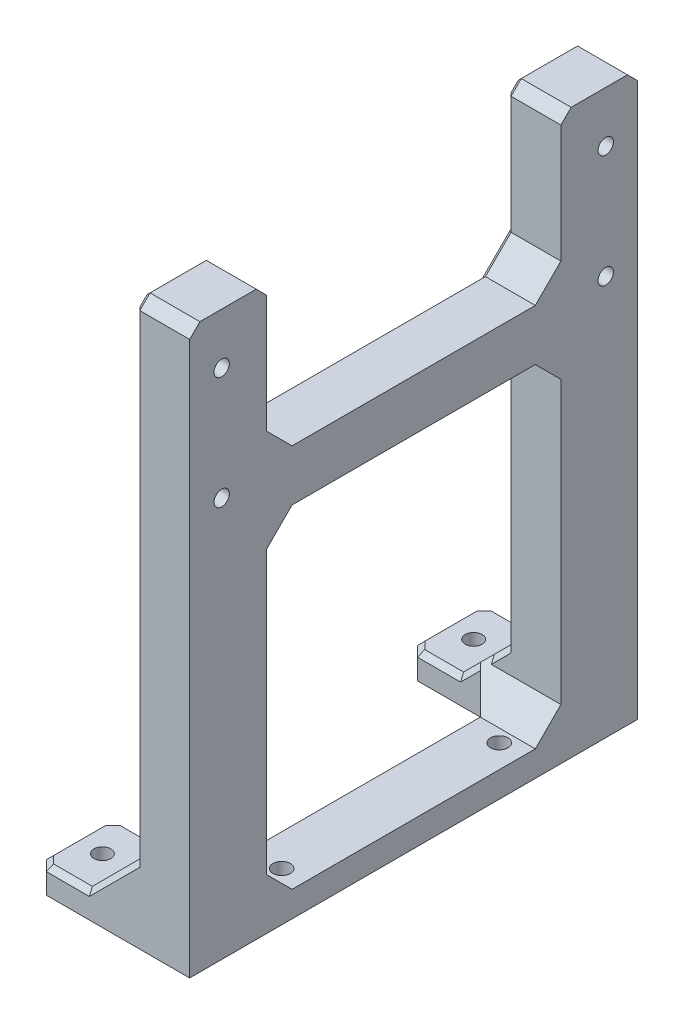
SolidWorks part; units mm, degrees
ref_plane "前视基准面" through (0, 0, 0) normal (0, 0, 1) x (1, 0, 0)
ref_plane "上视基准面" through (0, 0, 0) normal (0, 1, 0) x (1, 0, 0)
ref_plane "右视基准面" through (0, 0, 0) normal (1, 0, 0) x (0, 0, -1)
other "Configuration Table"
sketch "草图1" plane through (0, 0, 0) normal (0, 0, 1) x (1, 0, 0)
  line L0 (0, 110) -> (0, 0)
  line L1 (0, 0) -> (-30, 0)
  line L2 (-30, 0) -> (-30, 5)
  line L5 (-10.743, 14.257) -> (-10.743, 110)
  line L6 (-10.743, 110) -> (0, 110)
  line L7 (-30, 5) -> (-20, 5)
  line L8 (-20, 5) -> (-10.743, 14.257)
  dimension "D1" = 110
  dimension "D2" = 30
  dimension "D3" = 5
  dimension "D4" = 135
  dimension "D5" = 10
extrude "凸台-拉伸1" add sketch "草图1" along normal blind 15
ref_plane "基准面7" through (0, 0, -28.75) normal (0, 0, 1) x (1, 0, 0)
mirror "镜向9" about plane through (0, 0, -28.75) normal (0, 0, 1) of bodies 106
sketch "草图3" plane through (0, 0, -57.5) normal (0, 0, 1) x (1, 0, 0)
  line L0 (-10.743, 110) -> (-10.743, 14.257) construction
  line L1 (-10.743, 80) -> (0, 80)
  line L2 (-10.743, 80) -> (-10.743, 70)
  line L3 (-10.743, 70) -> (0, 70)
  line L4 (0, 80) -> (0, 70)
  line L5 (0, 0) -> (0, 110) construction
  line L6 (0, 110) -> (-10.743, 110) construction
  dimension "D1" = 10
  dimension "D2" = 30
extrude "凸台-拉伸2" add sketch "草图3" along normal up to surface (57.5 mm away) up to face at (-14.498, 34.8939, 0)
sketch "草图4" plane through (0, 0, -57.5) normal (0, 0, 1) x (1, 0, 0)
  line L0 (0, 0) -> (0, 110) construction
  line L1 (0, 5) -> (-10.743, 5)
  line L2 (0, 5) -> (0, 0)
  line L3 (0, 0) -> (-10.743, 0)
  line L4 (-10.743, 5) -> (-10.743, 0)
  line L5 (-30, 0) -> (0, 0) construction
  line L6 (-10.743, 110) -> (-10.743, 14.257) construction
  dimension "D1" = 5
extrude "凸台-拉伸3" add sketch "草图4" along normal up to surface (57.5 mm away) up to face at (-14.498, 23.4653, 0)
sketch "草图5" plane through (0, 5, 0) normal (0, 1, 0) x (1, 0, 0)
  line L0 (0, 28.75) -> (-65.0702, 28.75) construction
  line L1 (0, 0) -> (0, 57.5) construction
  line L2 (-16.5, 28.75) -> (16.5, 28.75) construction
  circle A0 centre (-24.5372, 65) radius 1.65
  circle A1 centre (-24.5372, -7.5) radius 1.65
  dimension "D1" = 3.3
  dimension "D2" = 72.5
extrude "切除-拉伸1" cut sketch "草图5" against normal up to next
sketch "草图6" plane through (0, 0, 0) normal (0, -1, 0) x (1, 0, 0)
  line L0 (16.5, -28.75) -> (-16.5, -28.75) construction
  line L1 (0, -28.75) -> (29.9701, -28.75) construction
  line L2 (0, 15) -> (0, -72.5) construction
  circle A0 centre (-4.5372, -7.5) radius 1.7
  circle A1 centre (-4.5372, -50) radius 1.7
  circle A2 centre (-24.5372, 7.5) radius 1.65 construction
  dimension "D1" = 20
  dimension "D2" = 15
  dimension "D3" = 3.4
extrude "切除-拉伸2" cut sketch "草图6" against normal up to next
sketch "草图7" plane through (-10.743, 0, 0) normal (-1, 0, 0) x (0, 0, 1)
  line L0 (-28.75, 80) -> (-28.75, 143.701) construction
  line L1 (0, 80) -> (-57.5, 80) construction
  line L2 (-28.75, -16.5) -> (-28.75, 16.5) construction
  line L3 (-72.5, 0) -> (-57.5, 0) construction
  circle A0 centre (-66.25, 100.05) radius 1.5
  circle A1 centre (8.75, 100.05) radius 1.5
  circle A2 centre (-66.25, 78.05) radius 1.5
  circle A3 centre (8.75, 78.05) radius 1.5
  dimension "D1" = 3
  dimension "D2" = 100.05
  dimension "D3" = 75
  dimension "D4" = 3
  dimension "D5" = 22
extrude "切除-拉伸3" cut sketch "草图7" against normal up to next
chamfer "倒角1" distance 5 angle 45 6 edges at (-5.3715, 5, 0) (-5.3715, 5, -57.5) (-5.3715, 70, -57.5) (-5.3715, 70, 0) (-5.3715, 80, 0) (-5.3715, 80, -57.5)
chamfer "倒角2" distance 2 angle 45 8 edges at (-5.3715, 110, 15) (-5.3715, 110, 0) (-5.3715, 110, -57.5) (-5.3715, 110, -72.5) (-30, 2.5, 15) (-30, 2.5, 0) (-30, 2.5, -57.5) (-30, 2.5, -72.5)
chamfer "倒角3" distance 5 angle 45 2 edges at (-10.743, 5, 0) (-10.743, 5, -57.5)
chamfer "倒角4" distance 1 angle 45 34 edges at (-12.8715, 12.1285, 0) (-10.743, 39.6285, 0) (-17.8715, 7.1285, 0) (-24, 5, 0) (-29, 5, 1) (-30, 5, 7.5) (-29, 5, 14) (-24, 5, 15) (-15.3715, 9.6285, 15) (-10.743, 61.1285, 15) (-10.743, 109, 14) (-10.743, 110, 7.5) (-10.743, 109, 1) (-10.743, 96.5, 0) (-10.743, 39.6285, -57.5) (-12.8715, 12.1285, -57.5) (-10.743, 96.5, -57.5) (-10.743, 109, -58.5) (-10.743, 110, -65) (-10.743, 109, -71.5) (-17.8715, 7.1285, -57.5) (-24, 5, -57.5) (-29, 5, -58.5) (-30, 5, -65) (-29, 5, -71.5) (-24, 5, -72.5) (-15.3715, 9.6285, -72.5) (-10.743, 61.1285, -72.5) (-10.743, 67.5, -2.5) (-10.743, 70, -28.75) (-10.743, 67.5, -55) (-10.743, 82.5, -2.5) (-10.743, 80, -28.75) (-10.743, 82.5, -55)
